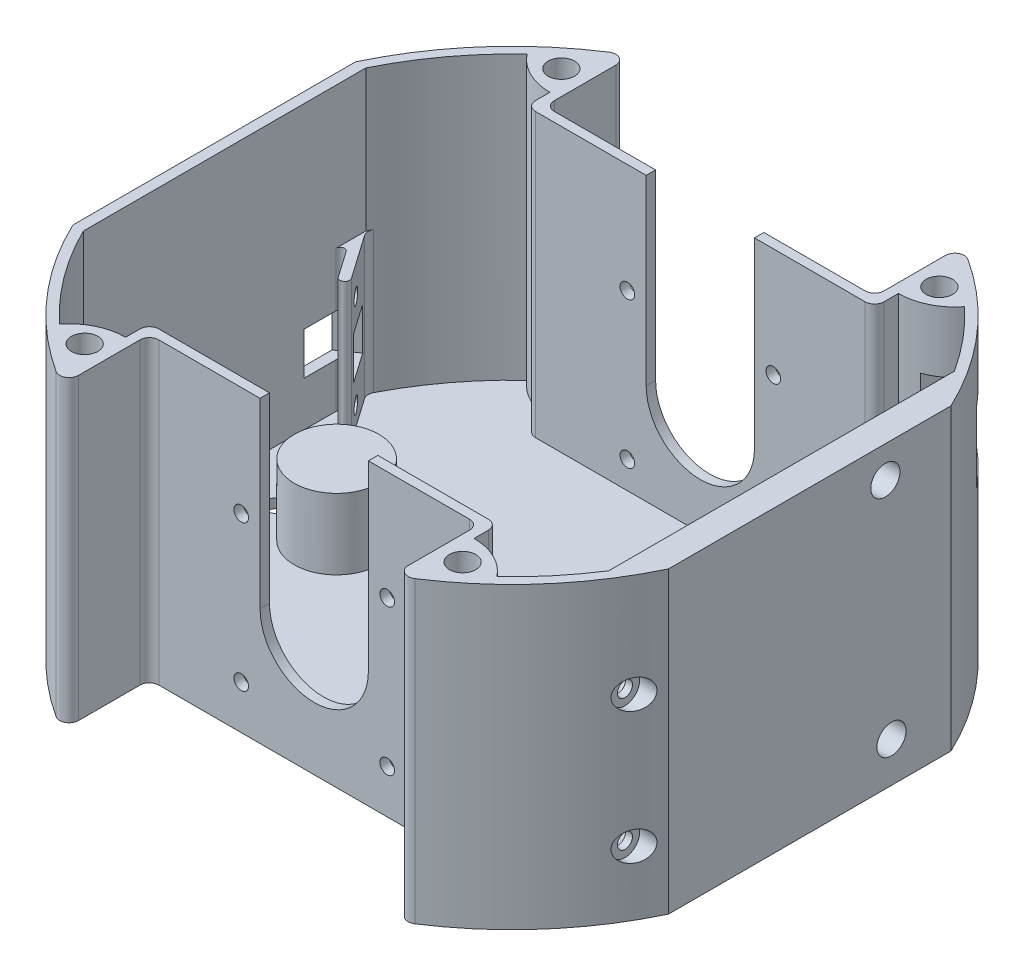
SolidWorks part; units mm, degrees
ref_plane "Plan de face" through (0, 0, 0) normal (0, 0, 1) x (1, 0, 0)
ref_plane "Plan de dessus" through (0, 0, 0) normal (0, 1, 0) x (1, 0, 0)
ref_plane "Plan de droite" through (0, 0, 0) normal (1, 0, 0) x (0, 0, -1)
sketch "Esquisse1" plane through (0, 0, 0) normal (0, 1, 0) x (1, 0, 0)
  line L0 (0, 7.0991) -> (0, -9.5713) construction
  line L1 (-20.3786, 0) -> (23.686, 0) construction
  line L2 (35, 42) -> (-35, 42)
  line L7 (-63.2456, -30) -> (-63.2456, 30)
  line L8 (-35, 42) -> (-35, 60.6218)
  line L9 (-21, 0) -> (-21, 42) construction
  line L12 (-35, -42) -> (-35, -60.6218)
  line L13 (35, -42) -> (-35, -42)
  line L15 (35, -42) -> (35, -60.6218)
  line L16 (63.2456, -30) -> (63.2456, 30)
  line L17 (35, 42) -> (35, 60.6218)
  circle A0 centre (0, 0) radius 70 construction
  arc A1 (-63.2456, 30) -> (-35, 60.6218) centre (0, 0) cw
  arc A2 (-63.2456, -30) -> (-35, -60.6218) centre (0, 0) ccw
  arc A3 (63.2456, -30) -> (35, -60.6218) centre (0, 0) cw
  arc A4 (63.2456, 30) -> (35, 60.6218) centre (0, 0) ccw
  circle A5 centre (-50, 0) radius 2.05
  circle A6 centre (50, 0) radius 2.05
  point P16 (-63.2456, 0)
  point P20 (0, -42)
  point P25 (0, 42)
  dimension "D1" = 140
  dimension "D2" = 42
  dimension "D6" = 4.1
  dimension "D3" = 35
  dimension "D4" = 30
  dimension "D5" = 21
  dimension "D7" = 50
extrude "Boss.-Extru.1" add sketch "Esquisse1" along normal blind 3.5
sketch "Esquisse3" plane through (0, 3.5, 0) normal (0, 1, 0) x (1, 0, 0)
  line L0 (-100.0452, 0) -> (128.6597, 0) construction
  line L1 (0, 78.0074) -> (0, -84.0534) construction
  line L2 (-61.0246, -30) -> (-61.0246, 30)
  line L3 (37, 40) -> (-37, 40)
  line L4 (-37, 40) -> (-37, 57.0526)
  line L5 (-63.2456, 30) -> (-61.0246, 30) construction
  line L6 (-37, -40) -> (-37, -57.0526)
  line L7 (37, -40) -> (-37, -40)
  line L8 (-35, 42) -> (-35, 60.6218)
  line L9 (-63.2456, 30) -> (-63.2456, -30)
  line L10 (-35, -60.6218) -> (-35, -42)
  line L11 (-35, -42) -> (35, -42)
  line L12 (35, -42) -> (35, -60.6218)
  line L13 (63.2456, -30) -> (63.2456, 30)
  line L14 (35, 60.6218) -> (35, 42)
  line L15 (35, 42) -> (-35, 42)
  line L16 (-35, 42) -> (-35, 60.6218)
  line L17 (-63.2456, 30) -> (-63.2456, -30)
  line L18 (-35, -60.6218) -> (-35, -42)
  line L19 (-35, -42) -> (35, -42)
  line L20 (35, -42) -> (35, -60.6218)
  line L21 (63.2456, -30) -> (63.2456, 30)
  line L22 (35, 60.6218) -> (35, 42)
  line L23 (35, 42) -> (-35, 42)
  line L24 (37, -40) -> (37, -57.0526)
  line L25 (61.0246, -30) -> (61.0246, 30)
  line L26 (37, 40) -> (37, 57.0526)
  line L27 (-61.0246, 30) -> (-52.4209, 17.7127)
  line L28 (-52.4209, 17.7127) -> (-54.0592, 16.5656)
  line L29 (-54.0592, 16.5656) -> (-61.0246, 26.5131)
  line L30 (-56.7228, 23.8564) -> (-177.37, -60.6218) construction
  line L31 (-52.4209, -17.7127) -> (-54.0592, -16.5656)
  line L32 (-61.0246, -30) -> (-52.4209, -17.7127)
  line L33 (-54.0592, -16.5656) -> (-61.0246, -26.5131)
  line L34 (-56.7228, -23.8564) -> (-177.37, 60.6218) construction
  line L35 (57.2456, 36.7008) -> (57.2456, -36.7008)
  line L36 (51.2707, 60.6218) -> (-111.4939, 60.6218) construction
  line L37 (51.2707, -60.6218) -> (-111.4939, -60.6218) construction
  line L38 (-63.2456, 45.1535) -> (-63.2456, -75.8674) construction
  line L39 (-90.7199, 0) -> (-90.7199, -104.005) construction
  line L40 (-63.2456, -19.2891) -> (-177.37, 60.6218) construction
  line L41 (-109.3793, 70.4336) -> (-109.3793, -69.597) construction
  line L42 (-134.3793, 0) -> (-120.0399, 20.4788) construction
  circle A0 centre (0, 0) radius 68 construction
  arc A1 (-37, 57.0526) -> (-61.0246, 30) centre (0, 0) ccw
  arc A2 (-46.4527, 49.6603) -> (-37, 45.0526) centre (-37, 57.0526) ccw
  arc A3 (-37, -57.0526) -> (-61.0246, -30) centre (0, 0) cw
  arc A4 (-35, 60.6218) -> (-63.2456, 30) centre (0, 0) ccw
  arc A5 (-63.2456, -30) -> (-35, -60.6218) centre (0, 0) ccw
  arc A6 (35, -60.6218) -> (63.2456, -30) centre (0, 0) ccw
  arc A7 (63.2456, 30) -> (35, 60.6218) centre (0, 0) ccw
  arc A8 (-35, 60.6218) -> (-63.2456, 30) centre (0, 0) ccw
  arc A9 (-63.2456, -30) -> (-35, -60.6218) centre (0, 0) ccw
  arc A10 (35, -60.6218) -> (63.2456, -30) centre (0, 0) ccw
  arc A11 (63.2456, 30) -> (35, 60.6218) centre (0, 0) ccw
  arc A12 (-46.4527, -49.6603) -> (-37, -45.0526) centre (-37, -57.0526) cw
  arc A13 (37, -57.0526) -> (61.0246, -30) centre (0, 0) ccw
  arc A14 (46.4527, -49.6603) -> (37, -45.0526) centre (37, -57.0526) ccw
  arc A15 (37, 57.0526) -> (61.0246, 30) centre (0, 0) cw
  arc A16 (46.4527, 49.6603) -> (37, 45.0526) centre (37, 57.0526) cw
  circle A17 centre (-134.3793, 0) radius 25 construction
  point P29 (-61.0246, 0)
  point P40 (0, -40)
  point P45 (0, 40)
  line M27 (-35, 42) -> (-35, 60.6218)
  arc M28 (-35, 60.6218) -> (-63.2456, 30) centre (0, 0) ccw
  line M29 (-63.2456, 30) -> (-63.2456, -30)
  arc M30 (-63.2456, -30) -> (-35, -60.6218) centre (0, 0) ccw
  line M31 (-35, -60.6218) -> (-35, -42)
  line M32 (-35, -42) -> (35, -42)
  line M33 (35, -42) -> (35, -60.6218)
  arc M34 (35, -60.6218) -> (63.2456, -30) centre (0, 0) ccw
  line M35 (63.2456, -30) -> (63.2456, 30)
  arc M36 (63.2456, 30) -> (35, 60.6218) centre (0, 0) ccw
  line M37 (35, 60.6218) -> (35, 42)
  line M38 (35, 42) -> (-35, 42)
  dimension "D2" = 136
  dimension "D3" = 2
  dimension "D5" = 12
  dimension "D13" = 50
  dimension "D4" = 2
  dimension "D6" = 2
  dimension "D7" = 15
  dimension "D8" = 35
  dimension "D9" = 6
  dimension "D10" = 139.3203
  dimension "D11" = 114.1245
  dimension "D12" = 27.4743
  dimension "D14" = 71.1338
  dimension "D15" = 46.1338
  dimension "D16" = 69.3331
  dimension "D17" = 7.9629
  dimension "D1" = 0
extrude "Boss.-Extru.2" add sketch "Esquisse3" along normal blind 60 contours L26 A15 L25 A13 L24 L7 L6 A3 L2 A1 L4 L3 M38 M27 M28 M29 M30 M31 M32 M33 M34 M35 M36 M37 | L29 L28 L27 L2 | A12 A3 L6 | A16 A15 L26 | A13 A14 L24 | L31 L33 L2 L32 | A15 L35 A13 L25 | A1 A2 L4 region at (-57.118, 3.5, 22.7385) region at (-40.4306, 3.5, 50.2104) region at (-57.118, 3.5, -22.7385) region at (-40.4306, 3.5, -50.2104) region at (40.4306, 3.5, 50.2104) region at (59.0722, 3.5, 0) region at (40.4306, 3.5, -50.2104) region at (0, 3.5, -40.2479)
sketch "Esquisse24" plane through (0, 63.5, 0) normal (0, 1, 0) x (1, 0, 0)
  line L0 (-61.0246, 30) -> (-61.0246, -30)
  line L1 (-61.0246, 30) -> (-52.4209, 17.7127) construction
  line L8 (35, 42) -> (-35, 42)
  line L9 (-35, 42) -> (-35, 60.6218)
  line L10 (-63.2456, 30) -> (-63.2456, -30)
  line L11 (-35, -60.6218) -> (-35, -42)
  line L12 (-35, -42) -> (35, -42)
  line L13 (35, -42) -> (35, -60.6218)
  line L14 (63.2456, -30) -> (63.2456, 30)
  line L15 (35, 60.6218) -> (35, 42)
  line L16 (35, 42) -> (-35, 42)
  line L17 (-35, 42) -> (-35, 60.6218)
  line L18 (-63.2456, 30) -> (-63.2456, -30)
  line L19 (-35, -60.6218) -> (-35, -42)
  line L20 (-35, -42) -> (35, -42)
  line L21 (35, -42) -> (35, -60.6218)
  line L22 (63.2456, -30) -> (63.2456, 30)
  line L23 (35, 60.6218) -> (35, 42)
  arc A4 (-35, 60.6218) -> (-63.2456, 30) centre (0, 0) ccw
  arc A5 (-63.2456, -30) -> (-35, -60.6218) centre (0, 0) ccw
  arc A6 (35, -60.6218) -> (63.2456, -30) centre (0, 0) ccw
  arc A7 (63.2456, 30) -> (35, 60.6218) centre (0, 0) ccw
  arc A8 (-35, 60.6218) -> (-63.2456, 30) centre (0, 0) ccw
  arc A9 (-63.2456, -30) -> (-35, -60.6218) centre (0, 0) ccw
  arc A10 (35, -60.6218) -> (63.2456, -30) centre (0, 0) ccw
  arc A11 (63.2456, 30) -> (35, 60.6218) centre (0, 0) ccw
  line M22 (-61.0246, -30) -> (-52.4209, -17.7127)
  line M23 (-52.4209, -17.7127) -> (-54.0592, -16.5656)
  line M24 (-54.0592, -16.5656) -> (-61.0246, -26.5131)
  line M26 (-61.0246, 26.5131) -> (-54.0592, 16.5656)
  line M27 (-54.0592, 16.5656) -> (-52.4209, 17.7127)
  line M28 (-52.4209, 17.7127) -> (-61.0246, 30)
  dimension "D1" = 0
extrude "Enlèv. mat.-Extru.14" cut sketch "Esquisse24" against normal blind 30 contours L0 M28 M26 M27 | L0 M24 M22 M23 region at (-57.118, 63.5, -22.7385) region at (-57.118, 63.5, 22.7385)
sketch "Esquisse4" plane through (0, 0, -40) normal (0, 0, 1) x (1, 0, 0)
  line L0 (0, -2.1196) -> (0, 67.1313) construction
  line L1 (0, 102.2) -> (0, 24.8) construction
  line L2 (11.5, 102.2) -> (11.5, 24.8)
  line L3 (-11.5, 102.2) -> (-11.5, 24.8)
  line L4 (-37, 3.5) -> (37, 3.5)
  line L5 (37, 3.5) -> (37, 63.5)
  line L6 (37, 63.5) -> (-37, 63.5)
  line L7 (-37, 63.5) -> (-37, 3.5)
  line L8 (-37, 3.5) -> (37, 3.5)
  line L9 (37, 3.5) -> (37, 63.5)
  line L10 (37, 63.5) -> (-37, 63.5)
  line L11 (-37, 63.5) -> (-37, 3.5)
  line L12 (-35, 0) -> (35, 0) construction
  line L13 (-35, 0) -> (35, 0)
  line L14 (31.9264, 24.8) -> (-22.6349, 24.8) construction
  arc A0 (11.5, 102.2) -> (-11.5, 102.2) centre (0, 102.2) ccw
  arc A1 (-11.5, 24.8) -> (11.5, 24.8) centre (0, 24.8) ccw
  circle A2 centre (-15.5, 40.3) radius 1.55
  circle A3 centre (-15.5, 9.3) radius 1.55
  circle A4 centre (15.5, 9.3) radius 1.55
  circle A5 centre (15.5, 40.3) radius 1.55
  point P9 (0, 63.5)
  line M14 (37, 63.5) -> (-37, 63.5)
  dimension "D3" = 15.5
  dimension "D5" = 3.1
  dimension "D2" = 23
  dimension "D4" = 15.5
  dimension "D6" = 21.3
  dimension "D7" = 24.8
  dimension "D1" = 0
extrude "Enlèv. mat.-Extru.1" cut sketch "Esquisse4" against normal through all both and the other way through all contours L3 A1 L2 M14 | A3 | A2 | A5 | A4 region at (0, 39.5649, -40) region at (-15.5, 40.3, -40) region at (-15.5, 9.3, -40) region at (15.5, 9.3, -40) region at (15.5, 40.3, -40)
sketch "Esquisse7" plane through (0, 63.5, 0) normal (0, 1, 0) x (1, 0, 0)
  line L0 (-35, -60.6218) -> (-49.7114, -60.6218) construction
  line L1 (-46.4527, -49.6603) -> (-37, -45.0526) construction
  line L2 (-41.7264, -47.3565) -> (-37, -57.0526) construction
  line L12 (-11.5, 40) -> (-11.5, 42)
  line L13 (-11.5, 42) -> (-35, 42)
  line L14 (-35, 42) -> (-35, 60.6218)
  line L15 (-63.2456, 30) -> (-63.2456, -30)
  line L16 (-35, -60.6218) -> (-35, -42)
  line L17 (-35, -42) -> (-11.5, -42)
  line L24 (-11.5, 40) -> (-11.5, 42)
  line L25 (-11.5, 42) -> (-35, 42)
  line L26 (-35, 42) -> (-35, 60.6218)
  line L27 (-63.2456, 30) -> (-63.2456, -30)
  line L28 (-35, -60.6218) -> (-35, -42)
  line L29 (-35, -42) -> (-11.5, -42)
  line L39 (-11.5, -42) -> (-11.5, -40)
  line L41 (-11.5, -42) -> (-11.5, -40)
  line L43 (-11.5, -40) -> (-37, -40)
  line L45 (-11.5, -40) -> (-37, -40)
  line L47 (-37, -40) -> (-37, -45.0526)
  line L49 (-37, -40) -> (-37, -45.0526)
  line L51 (-61.0246, -30) -> (-61.0246, 30)
  line L53 (-61.0246, -30) -> (-61.0246, 30)
  line L55 (-37, 45.0526) -> (-37, 40)
  line L57 (-37, 45.0526) -> (-37, 40)
  line L59 (-37, 40) -> (-11.5, 40)
  line L61 (-37, 40) -> (-11.5, 40)
  circle A1 centre (-40.1347, -50.6218) radius 2.8
  circle A2 centre (-40.1347, -50.6218) radius 4.8
  arc A6 (-35, 60.6218) -> (-63.2456, 30) centre (0, 0) ccw
  arc A7 (-63.2456, -30) -> (-35, -60.6218) centre (0, 0) ccw
  arc A9 (-37, -45.0526) -> (-46.4527, -49.6603) centre (-37, -57.0526) ccw
  arc A10 (-37, -45.0526) -> (-46.4527, -49.6603) centre (-37, -57.0526) ccw
  arc A12 (-35, 60.6218) -> (-63.2456, 30) centre (0, 0) ccw
  arc A13 (-63.2456, -30) -> (-35, -60.6218) centre (0, 0) ccw
  arc A18 (-61.0246, -30) -> (-46.4527, -49.6603) centre (0, 0) ccw
  arc A20 (-61.0246, -30) -> (-46.4527, -49.6603) centre (0, 0) ccw
  arc A22 (-46.4527, 49.6603) -> (-61.0246, 30) centre (0, 0) ccw
  arc A24 (-46.4527, 49.6603) -> (-61.0246, 30) centre (0, 0) ccw
  arc A26 (-46.4527, 49.6603) -> (-37, 45.0526) centre (-37, 57.0526) ccw
  arc A27 (-46.4527, 49.6603) -> (-37, 45.0526) centre (-37, 57.0526) ccw
  dimension "D2" = 5.6
  dimension "D3" = 10
  dimension "D5" = 9.6
  dimension "D4" = 5.1347
  dimension "D1" = 0
extrude "Enlèv. mat.-Extru.2" cut sketch "Esquisse7" against normal blind 9.1 contours A1
sketch "Esquisse8" plane through (-35, 0, 0) normal (1, 0, 0) x (0, 0, -1)
  line L1 (-47.0218, 55.3) -> (-54.2218, 55.3)
  line L2 (-47.0218, 55.3) -> (-47.0218, 58.5)
  line L3 (-47.0218, 58.5) -> (-54.2218, 58.5)
  line L4 (-60.6218, 0) -> (-42, 0)
  line L5 (-42, 0) -> (-42, 63.5)
  line L6 (-42, 63.5) -> (-60.6218, 63.5)
  line L7 (-60.6218, 63.5) -> (-60.6218, 0)
  line L8 (-60.6218, 0) -> (-42, 0)
  line L9 (-42, 0) -> (-42, 63.5)
  line L10 (-42, 63.5) -> (-60.6218, 63.5)
  line L11 (-60.6218, 63.5) -> (-60.6218, 0)
  line L12 (-54.2218, 55.3) -> (-54.2218, 58.5)
  line L13 (-47.0218, 55.3) -> (-54.2218, 58.5) construction
  line L14 (-47.0218, 58.5) -> (-54.2218, 55.3) construction
  point P2 (-50.6218, 56.9)
  dimension "D2" = 10
  dimension "D3" = 7.2
  dimension "D4" = 3.2
  dimension "D5" = 5
  dimension "D1" = 0
extrude "Enlèv. mat.-Extru.3" [suppressed] cut sketch "Esquisse8" against normal blind 5 contours L2 L1 L12 L3
sketch "Esquisse10" plane through (0, 63.5, 0) normal (0, 1, 0) x (1, 0, 0)
  line L0 (-40.1347, -50.6218) -> (-35, -50.6218) construction
  line L1 (-35.9778, -50.6218) -> (-38.0562, -47.0218)
  line L2 (-38.0562, -47.0218) -> (-42.2131, -47.0218)
  line L3 (-42.2131, -47.0218) -> (-44.2916, -50.6218)
  line L4 (-44.2916, -50.6218) -> (-42.2131, -54.2218)
  line L5 (-42.2131, -54.2218) -> (-38.0562, -54.2218)
  line L6 (-38.0562, -54.2218) -> (-35.9778, -50.6218)
  line L7 (-35, -60.6218) -> (-35, -42) construction
  circle A0 centre (-40.1347, -50.6218) radius 2.8 construction
  circle A1 centre (-40.1347, -50.6218) radius 2.8
  circle A2 centre (-40.1347, -50.6218) radius 3.6 construction
  dimension "D1" = 7.2
extrude "Enlèv. mat.-Extru.4" [suppressed] cut sketch "Esquisse10" against normal blind 3.2 from offset 5
mirror "Symétrie1" about plane through (0, 0, 0) normal (1, 0, 0) of "Enlèv. mat.-Extru.4", "Enlèv. mat.-Extru.3", "Enlèv. mat.-Extru.2"
mirror "Symétrie2" about plane through (0, 0, 0) normal (0, 0, 1) of "Symétrie1", "Enlèv. mat.-Extru.4", "Enlèv. mat.-Extru.3", "Enlèv. mat.-Extru.2"
sketch "Esquisse26" plane through (0, 3.5, 0) normal (0, 1, 0) x (1, 0, 0)
  line L0 (-79.6813, 0) -> (102.9554, 0) construction
  line L1 (-63.2456, 30) -> (-63.2456, -30) construction
  line L2 (-42.2456, 10) -> (-32.2456, 10) construction
  line L3 (-42.2456, 10) -> (-42.2456, -10) construction
  line L4 (-42.2456, -10) -> (-32.2456, -10) construction
  line L5 (-32.2456, 10) -> (-32.2456, -10) construction
  line L6 (-42.2456, 10) -> (-32.2456, -10) construction
  line L7 (-42.2456, -10) -> (-32.2456, 10) construction
  line L8 (-63.2456, 30) -> (-63.2456, -30)
  line L11 (-28.2456, -5) -> (-46.2456, -5) construction
  line L12 (-28.2456, -5) -> (-28.2456, 5) construction
  line L13 (-28.2456, 5) -> (-46.2456, 5) construction
  line L14 (-61.0246, 30) -> (-52.4209, 17.7127)
  line L15 (-52.4209, 17.7127) -> (-54.0592, 16.5656)
  line L16 (-54.0592, 16.5656) -> (-61.0246, 26.5131)
  line L17 (-61.0246, 26.5131) -> (-61.0246, -26.5131)
  line L18 (-61.0246, -26.5131) -> (-54.0592, -16.5656)
  line L19 (-52.4209, 17.7127) -> (-54.0592, 16.5656)
  line L20 (-52.4209, -17.7127) -> (-61.0246, -30)
  line L21 (-37, -45.0526) -> (-37, -40)
  line L22 (-37, -40) -> (37, -40)
  line L23 (37, -40) -> (37, -45.0526)
  line L24 (57.2456, -36.7008) -> (57.2456, 36.7008)
  line L25 (37, 45.0526) -> (37, 40)
  line L26 (37, 40) -> (-37, 40)
  line L27 (-37, 40) -> (-37, 45.0526)
  line L28 (-61.0246, 30) -> (-52.4209, 17.7127)
  line L30 (-54.0592, 16.5656) -> (-61.0246, 26.5131)
  line L31 (-61.0246, 26.5131) -> (-61.0246, -26.5131)
  line L32 (-61.0246, -26.5131) -> (-54.0592, -16.5656)
  line L34 (-52.4209, -17.7127) -> (-61.0246, -30)
  line L35 (-37, -45.0526) -> (-37, -40)
  line L36 (-37, -40) -> (37, -40)
  line L37 (37, -40) -> (37, -45.0526)
  line L38 (57.2456, -36.7008) -> (57.2456, 36.7008)
  line L39 (37, 45.0526) -> (37, 40)
  line L40 (37, 40) -> (-37, 40)
  line L41 (-37, 40) -> (-37, 45.0526)
  line L42 (-46.2456, -5) -> (-46.2456, 5) construction
  line L43 (-28.2456, -5) -> (-46.2456, 5) construction
  line L44 (-28.2456, 5) -> (-46.2456, -5) construction
  line L49 (-54.0592, -16.5656) -> (-52.4209, -17.7127)
  line L50 (-54.0592, -16.5656) -> (-52.4209, -17.7127)
  circle A0 centre (-37.2456, 0) radius 9
  arc A23 (-61.0246, -30) -> (-46.4527, -49.6603) centre (0, 0) ccw
  arc A24 (-37, -45.0526) -> (-46.4527, -49.6603) centre (-37, -57.0526) ccw
  arc A27 (46.4527, -49.6603) -> (37, -45.0526) centre (37, -57.0526) ccw
  arc A28 (46.4527, -49.6603) -> (57.2456, -36.7008) centre (0, 0) ccw
  arc A29 (57.2456, 36.7008) -> (46.4527, 49.6603) centre (0, 0) ccw
  arc A30 (37, 45.0526) -> (46.4527, 49.6603) centre (37, 57.0526) ccw
  arc A33 (-46.4527, 49.6603) -> (-37, 45.0526) centre (-37, 57.0526) ccw
  arc A34 (-46.4527, 49.6603) -> (-61.0246, 30) centre (0, 0) ccw
  arc A41 (-61.0246, -30) -> (-46.4527, -49.6603) centre (0, 0) ccw
  arc A42 (-37, -45.0526) -> (-46.4527, -49.6603) centre (-37, -57.0526) ccw
  arc A45 (46.4527, -49.6603) -> (37, -45.0526) centre (37, -57.0526) ccw
  arc A46 (46.4527, -49.6603) -> (57.2456, -36.7008) centre (0, 0) ccw
  arc A47 (57.2456, 36.7008) -> (46.4527, 49.6603) centre (0, 0) ccw
  arc A48 (37, 45.0526) -> (46.4527, 49.6603) centre (37, 57.0526) ccw
  arc A51 (-46.4527, 49.6603) -> (-37, 45.0526) centre (-37, 57.0526) ccw
  arc A52 (-46.4527, 49.6603) -> (-61.0246, 30) centre (0, 0) ccw
  point P9 (-37.2456, 0)
  point P20 (-37.2456, 0)
  dimension "D2" = 10
  dimension "D3" = 20
  dimension "D4" = 26
  dimension "D5" = 18
  dimension "D1" = 0
extrude "Boss.-Extru.4" add sketch "Esquisse26" along normal blind 15 contours L5 L11 L3 L4 | L13 L5 L2 L3 | A0 region at (-37.2456, 3.5, 0)
fillet "Congé1" radius 2 14 edges at (37, 33.5, -40) (-35, 31.75, -42) (35, 31.75, -42) (-37, 33.5, -40) (-35, 31.75, -60.6218) (35, 31.75, -60.6218) (-37, 33.5, 40) (37, 33.5, 40) (35, 31.75, 42) (-35, 31.75, 42) (35, 31.75, 60.6218) (-35, 31.75, 60.6218) (-61.0246, 18.5, -30) (-61.0246, 18.5, 30) tangent propagation no
fillet "Congé2" radius 0.9 2 edges at (-61.0246, 18.5, -26.5131) (-61.0246, 18.5, 26.5131)
sketch "Esquisse13" plane through (0, 0, 0) normal (0, -1, 0) x (1, 0, 0)
  circle A0 centre (-50, 0) radius 2.05 construction
  circle A1 centre (-50, 0) radius 2.05
  circle A2 centre (50, 0) radius 2.05 construction
  circle A3 centre (50, 0) radius 2.05
  circle A4 centre (-50, 0) radius 12.75
  circle A5 centre (50, 0) radius 12.75
  dimension "D1" = 25.5
extrude "Enlèv. mat.-Extru.5" cut sketch "Esquisse13" against normal blind 1.5
sketch "Esquisse14" plane through (-26.8527, 0, -18.8025) normal (0.8192, 0, 0.5736) x (0.5736, 0, -0.8192)
  line L0 (-50.9268, 35) -> (-50.9268, 3.5) construction
  line L1 (-44.5768, 17.5) -> (-59.5768, 17.5) construction
  line L2 (-45.5768, 35) -> (-45.5768, 3.5) construction
  line L4 (-44.5768, 33.5) -> (-58.3826, 33.5)
  line L5 (-44.5768, 33.5) -> (-58.3826, 33.5)
  line L6 (-58.3826, 3.5) -> (-44.5768, 3.5)
  line L7 (-44.5768, 3.5) -> (-44.5768, 33.5)
  line L10 (-58.3826, 3.5) -> (-44.5768, 3.5)
  line L15 (-56.7768, 22) -> (-48.7768, 22)
  line L16 (-56.7768, 22) -> (-56.7768, 13)
  line L17 (-56.7768, 13) -> (-48.7768, 13)
  line L18 (-48.7768, 22) -> (-48.7768, 13)
  line L19 (-56.7768, 22) -> (-48.7768, 13) construction
  line L20 (-56.7768, 13) -> (-48.7768, 22) construction
  line L25 (-58.3826, 33.5) -> (-58.3826, 3.5)
  line L27 (-58.3826, 33.5) -> (-58.3826, 3.5)
  line L29 (-44.5768, 3.5) -> (-44.5768, 33.5)
  circle A0 centre (-50.9268, 27.5) radius 1.55
  circle A2 centre (-50.9268, 7.5) radius 1.55
  point P12 (-50.9268, 17.5)
  point P13 (-52.7768, 17.5)
  dimension "D2" = 20
  dimension "D3" = 3.1
  dimension "D4" = 8
  dimension "D5" = 9
  dimension "D6" = 1
  dimension "D7" = 14
  dimension "D8" = 11.2
  dimension "D9" = 5.35
  dimension "D1" = 0
extrude "Enlèv. mat.-Extru.6" cut sketch "Esquisse14" against normal blind 4.9 contours L17 L18 L15 L16 | A0 | A2
sketch "Esquisse16" plane through (-26.8527, 0, -18.8025) normal (0.8192, 0, 0.5736) x (0.5736, 0, -0.8192)
  line L0 (-48.7768, 22) -> (-48.7768, 13) construction
  line L1 (-56.7768, 22) -> (-48.7768, 22) construction
  line L2 (-56.7768, 22) -> (-56.7768, 13) construction
  line L3 (-56.7768, 13) -> (-48.7768, 13) construction
  line L4 (-48.7768, 22) -> (-48.7768, 13)
  line L5 (-56.7768, 22) -> (-48.7768, 22)
  line L6 (-56.7768, 22) -> (-56.7768, 13)
  line L7 (-56.7768, 13) -> (-48.7768, 13)
extrude "Enlèv. mat.-Extru.8" cut sketch "Esquisse16" against normal through all
mirror "Symétrie3" about plane through (0, 0, 0) normal (0, 0, 1) of "Enlèv. mat.-Extru.8", "Enlèv. mat.-Extru.6"
sketch "Esquisse18" plane through (57.2456, 0, 0) normal (-1, 0, 0) x (0, 0, 1)
  line L0 (-16.05, 59.34) -> (-16.05, 6) construction
  line L1 (37.29, 6) -> (-31.29, 6) construction
  line L4 (-36.7008, 3.5) -> (36.7008, 3.5)
  line L5 (36.7008, 3.5) -> (36.7008, 63.5)
  line L6 (36.7008, 63.5) -> (-36.7008, 63.5)
  line L7 (-36.7008, 63.5) -> (-36.7008, 3.5)
  line L8 (-36.7008, 3.5) -> (36.7008, 3.5) construction
  line L9 (36.7008, 3.5) -> (36.7008, 63.5) construction
  line L10 (36.7008, 63.5) -> (-36.7008, 63.5) construction
  line L11 (-36.7008, 63.5) -> (-36.7008, 3.5) construction
  line L14 (37.29, 6) -> (37.29, 59.34) construction
  line L16 (-30, 0) -> (30, 0) construction
  line L17 (37.29, 59.34) -> (-31.29, 59.34) construction
  line L18 (-31.29, 6) -> (-31.29, 59.34) construction
  line L19 (37.29, 6) -> (-31.29, 59.34) construction
  line L20 (37.29, 59.34) -> (-31.29, 6) construction
  line L21 (34.75, 59.34) -> (34.75, 6) construction
  line L22 (-17.35, 59.34) -> (-17.35, 6) construction
  circle A4 centre (-16.05, 56.8) radius 1.6
  circle A5 centre (-17.35, 8.54) radius 1.6
  circle A6 centre (34.75, 41.56) radius 1.6
  circle A7 centre (34.75, 13.62) radius 1.6
  point P4 (3, 32.67)
  dimension "D2" = 3.2
  dimension "D3" = 2.54
  dimension "D4" = 50.8
  dimension "D5" = 53.34
  dimension "D6" = 68.58
  dimension "D7" = 15.24
  dimension "D8" = 66.04
  dimension "D9" = 17.78
  dimension "D10" = 45.72
  dimension "D11" = 6
  dimension "D12" = 3
  dimension "D13" = 1.3
  dimension "D1" = 0
extrude "Enlèv. mat.-Extru.10" cut sketch "Esquisse18" against normal blind 10 and the other way blind 2.5
sketch "Esquisse19" plane through (63.2456, 0, 0) normal (1, 0, 0) x (0, 0, -1)
  circle A0 centre (17.35, 8.54) radius 1.6 construction
  circle A3 centre (16.05, 56.8) radius 1.6 construction
  circle A4 centre (17.35, 8.54) radius 1.6
  circle A7 centre (16.05, 56.8) radius 1.6
  circle A8 centre (-34.75, 41.56) radius 3.1
  circle A9 centre (16.05, 56.8) radius 3.1
  circle A10 centre (-34.75, 13.62) radius 3.1
  circle A11 centre (17.35, 8.54) radius 3.1
  circle A12 centre (-34.75, 13.62) radius 1.6 construction
  circle A13 centre (-34.75, 41.56) radius 1.6 construction
  circle A14 centre (-34.75, 13.62) radius 1.6
  circle A15 centre (-34.75, 41.56) radius 1.6
  dimension "D1" = 6.2
extrude "Enlèv. mat.-Extru.11" cut sketch "Esquisse19" against normal blind 4.5
sketch "Esquisse20" plane through (0, 0, 0) normal (0, -1, 0) x (1, 0, 0)
  line L0 (0, 42) -> (0, -42) construction
  line L1 (-33, 42) -> (33, 42) construction
  line L2 (33, -42) -> (-33, -42) construction
  text T0 "PIXEL V1" font "Century Gothic" height in points 26
extrude "Enlèv. mat.-Extru.12" cut sketch "Esquisse20" against normal blind 0.2
chamfer "Chanfrein1" distance 2 angle 55 2 edges at (-54.0592, 18.5, -16.5656) (-54.0592, 18.5, 16.5656) first distance on face at (-56.8124, 7.5, -20.4975) first distance on face at (-53.2401, 18.5, 17.1391)
sketch "Esquisse21" plane through (0, 0, 0) normal (0, 0, 1) x (1, 0, 0)
  line L0 (40.9956, 63.5) -> (40.9956, 35.5)
  line L1 (40.9956, 35.5) -> (53.4956, 35.5)
  line L2 (53.4956, 35.5) -> (53.4956, 63.5)
  line L3 (40.9956, 50.5) -> (53.4956, 50.5)
  line L4 (63.2456, 63.5) -> (38.0882, 63.5)
  line L5 (38.0882, 63.5) -> (38.0882, 0)
  line L6 (38.0882, 0) -> (63.2456, 0)
  line L7 (63.2456, 0) -> (63.2456, 63.5)
  line L8 (63.2456, 63.5) -> (38.0882, 63.5)
  line L10 (38.0882, 0) -> (63.2456, 0)
  line L11 (63.2456, 0) -> (63.2456, 63.5)
  line L17 (38.0882, 63.5) -> (38.0882, 0)
  dimension "D2" = 9.75
  dimension "D3" = 12.5
  dimension "D4" = 28
  dimension "D5" = 15
  dimension "D1" = 0
extrude "Enlèv. mat.-Extru.13" cut sketch "Esquisse21" against normal through all contours L3 L0 L1 L2 region at (47.2456, 43, 0)
fillet "Congé3" radius 1 2 edges at (-52.4209, 18.5, 17.7127) (-52.7648, 18.5, -18.2039)
sketch "Esquisse27" plane through (-27.9772, 0, 39.9556) normal (-0.5736, 0, 0.8192) x (0.8192, 0, 0.5736)
  line L4 (-34.7811, 22) -> (-34.7811, 13)
  line L5 (-34.7811, 13) -> (-32.7811, 13)
  line L6 (-32.7811, 13) -> (-32.7811, 22)
  line L7 (-32.7811, 22) -> (-34.7811, 22)
  line L8 (-34.7811, 22) -> (-34.7811, 13)
  line L9 (-34.7811, 13) -> (-32.7811, 13)
  line L10 (-32.7811, 13) -> (-32.7811, 22)
  line L11 (-32.7811, 22) -> (-34.7811, 22)
  dimension "D1" = 0
extrude "Boss.-Extru.5" add sketch "Esquisse27" along normal blind 1
